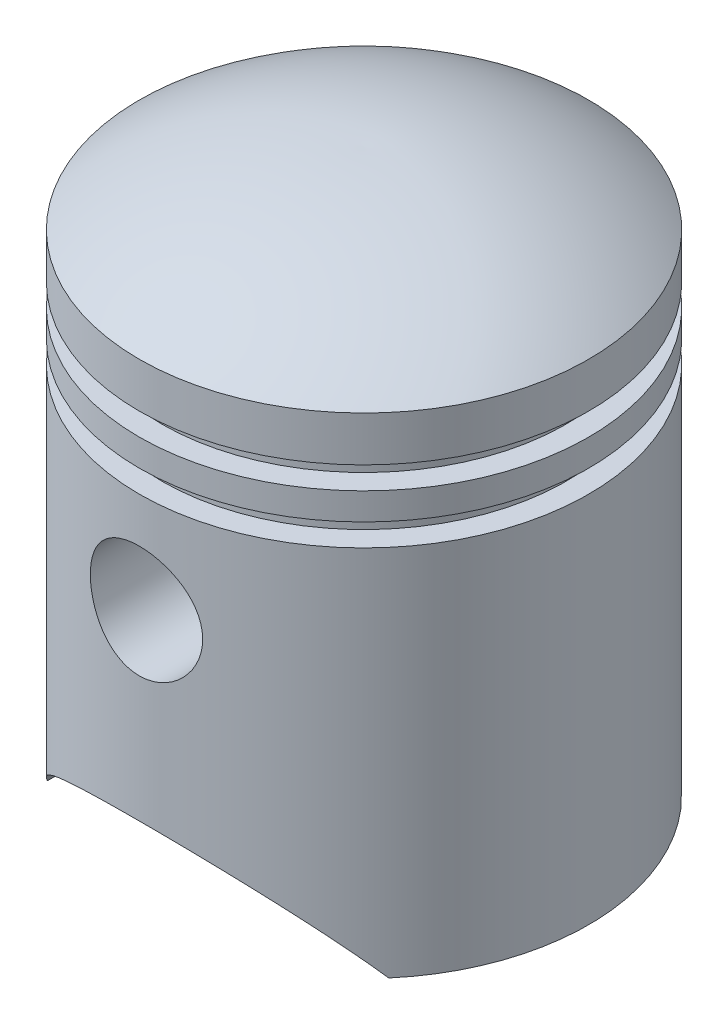
SolidWorks part; units mm, degrees
ref_plane "Front Plane" through (0, 0, 0) normal (0, 0, 1) x (1, 0, 0)
ref_plane "Top Plane" through (0, 0, 0) normal (0, 1, 0) x (1, 0, 0)
ref_plane "Right Plane" through (0, 0, 0) normal (1, 0, 0) x (0, 0, -1)
sketch "Sketch1" plane through (0, 0, 0) normal (0, 0, 1) x (1, 0, 0)
  line L0 (25, 0) -> (25, 41.5)
  line L1 (25, 49.5) -> (22.5, 49.5)
  line L2 (22.5, 49.5) -> (22.5, 47)
  line L3 (22.5, 47) -> (25, 47)
  line L5 (25, 44) -> (22.5, 44)
  line L6 (22.5, 44) -> (22.5, 41.5)
  line L7 (22.5, 41.5) -> (25, 41.5)
  line L8 (25, 49.5) -> (25, 54.5)
  line L9 (25, 44) -> (25, 47)
  line L10 (23, 0) -> (23, 39.5)
  line L11 (20.5, 39.5) -> (23, 39.5)
  line L12 (20.5, 45.5) -> (20.5, 39.5)
  line L13 (20.5, 45.5) -> (20.5, 45.5)
  line L14 (20.5, 45.5) -> (20.5, 45.5)
  line L15 (20.5, 45.5) -> (20.5, 45.5)
  line L16 (20.5, 51.5) -> (20.5, 45.5)
  line L17 (23, 51.5) -> (20.5, 51.5)
  line L18 (23, 51.5) -> (23, 53.4845)
  line L19 (25, 0) -> (23, 0)
  line L21 (0, 62.5) -> (0, 60.4994)
  arc A0 (25, 54.5) -> (0, 62.5) centre (0.9839, 22.5121) ccw
  arc A1 (23, 53.4845) -> (0, 60.4994) centre (0.9839, 22.5121) ccw
  arc A2 (23, 53.4845) -> (0.0492, 60.5006) centre (0.9839, 22.5121) ccw construction
  dimension "D4" = 40
  dimension "D1" = 25
  dimension "D2" = 62.5
  dimension "D3" = 54.5
  dimension "D5" = 5
  dimension "D6" = 2.5
  dimension "D7" = 3
  dimension "D8" = 2.5
  dimension "D9" = 2.5
  dimension "D10" = 2
revolve "Revolve1" add sketch "Sketch1" angle 360 about L21
sketch "Sketch2" plane through (0, 0, 0) normal (0, 0, 1) x (1, 0, 0)
  line L0 (-25, 0) -> (25, 0) construction
  line L1 (0, 30.5) -> (0, 62.5) construction
  line L2 (0, 0) -> (0, 10) construction
  line L3 (-19, 0) -> (19, 0)
  circle A0 centre (0, 30.5) radius 6.25
  arc A1 (-19, 0) -> (19, 0) centre (0, -13.05) cw
  dimension "D1" = 12.5
  dimension "D4" = 10
  dimension "D2" = 32
  dimension "D3" = 38
extrude "Cut-Extrude2" cut sketch "Sketch2" against normal through all both and the other way through all contours A0 | A1 L3
sketch "Sketch3" plane through (0, 0, 0) normal (0, 0, 1) x (1, 0, 0)
  circle A0 centre (0, 30.5) radius 7.25
  dimension "D1" = 14.5
extrude "Boss-Extrude2" add sketch "Sketch3" along normal up to surface (11.9257 mm away) from offset 12 contours A0 up to face at (1.2224, 24.3707, -24.9701)
sketch "Sketch4" plane through (0, 0, 12) normal (0, 0, -1) x (-1, 0, 0)
  circle A0 centre (0, 30.5) radius 5.75
  circle A1 centre (0, 30.5) radius 6.25 construction
  dimension "D1" = 0.5
extrude "Cut-Extrude4" cut sketch "Sketch4" against normal blind 12
mirror "Mirror1" about plane through (0, 0, 0) normal (0, 0, 1) of "Cut-Extrude4", "Boss-Extrude2"
sketch "Sketch6" plane through (0, 0, -24) normal (0, 0, 1) x (1, 0, 0)
  circle A0 centre (0, 30.2443) radius 6.25
  dimension "D1" = 12.5
extrude "Cut-Extrude5" cut sketch "Sketch6" against normal through all both and the other way through all
